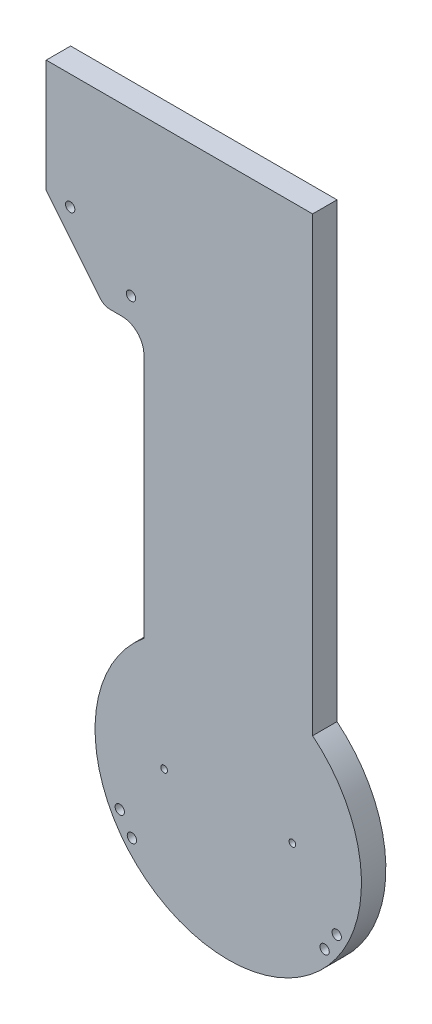
SolidWorks part; units mm, degrees
material "ﾁｰｸ材"
ref_plane "正面" through (0, 0, 0) normal (0, 0, 1) x (1, 0, 0)
ref_plane "平面" through (0, 0, 0) normal (0, 1, 0) x (1, 0, 0)
ref_plane "右側面" through (0, 0, 0) normal (1, 0, 0) x (0, 0, -1)
sketch "ｽｹｯﾁ1" plane through (0, 0, 0) normal (0, 0, 1) x (1, 0, 0)
  line L0 (19, 125) -> (-41, 125)
  line L1 (-19, 83.5651) -> (-19, 23.2164)
  line L2 (19, 125) -> (19, 23.2164)
  line L6 (-28, 83.5651) -> (-19, 83.5651)
  line L7 (-41, 99.5651) -> (-41, 125)
  line L8 (-28, 83.5651) -> (-41, 99.5651)
  arc A0 (-19, 23.2164) -> (19, 23.2164) centre (0, 0) ccw
  dimension "D1" = 60
  dimension "D2" = 125
  dimension "D3" = 19
  dimension "D4" = 13
  dimension "D5" = 41
  dimension "D6" = 16
extrude "ﾎﾞｽ - 押し出し1" add sketch "ｽｹｯﾁ1" along normal blind 5.5
sketch "ｽｹｯﾁ3" plane through (0, 0, 5.5) normal (0, 0, 1) x (1, 0, 0)
  line L0 (0, 0) -> (0, 22.4882) construction
fillet "ﾌｨﾚｯﾄ2" radius 5 1 edges at (-19, 83.5651, 2.75)
sketch "ｽｹｯﾁ5" plane through (0, 0, 5.5) normal (0, 0, 1) x (1, 0, 0)
  circle A0 centre (14.45, 0) radius 0.75
  circle A1 centre (-14.45, 0) radius 0.75
  dimension "D1" = 14.45
  dimension "D2" = 1.5
  dimension "D3" = 14.45
extrude "ｶｯﾄ - 押し出し3" cut sketch "ｽｹｯﾁ5" against normal through all
sketch "ｽｹｯﾁ6" plane through (0, 0, 5.5) normal (0, 0, 1) x (1, 0, 0)
  line L0 (0, 0) -> (-25.1601, -16.3392) construction
  line L1 (0, 0) -> (0, 22.4882) construction
  line L2 (-21.7018, -17.0742) -> (-24.425, -12.8809) construction
  line L3 (0, 0) -> (0, -5.9449) construction
  arc A0 (-19, 23.2164) -> (19, 23.2164) centre (0, 0) ccw construction
  circle A1 centre (-24.425, -12.8809) radius 1.05
  circle A2 centre (-21.7018, -17.0742) radius 1.05
  circle A3 centre (24.425, -12.8809) radius 1.05
  circle A4 centre (21.7018, -17.0742) radius 1.05
  point P12 (-23.0634, -14.9776)
  dimension "D2" = 5
  dimension "D3" = 2.1
  dimension "D4" = 2.1
  dimension "D1" = 123
  dimension "D5" = 27.5
extrude "ｶｯﾄ - 押し出し4" cut sketch "ｽｹｯﾁ6" against normal through all
sketch "ｽｹｯﾁ7" plane through (0, 0, 5.5) normal (0, 0, 1) x (1, 0, 0)
  line L0 (0, 0) -> (0, 22.4882) construction
  line L1 (-28, 83.5651) -> (-24, 83.5651) construction
  circle A0 centre (-21.9, 88.5651) radius 1.05
  circle A1 centre (-35.6, 99.0651) radius 1.05
  dimension "D1" = 2.1
  dimension "D3" = 13.7
  dimension "D5" = 5
  dimension "D2" = 21.9
  dimension "D4" = 10.5
extrude "ｶｯﾄ - 押し出し5" cut sketch "ｽｹｯﾁ7" against normal through all
fillet "ﾌｨﾚｯﾄ3" radius 3 1 edges at (-28, 83.5651, 2.75)
